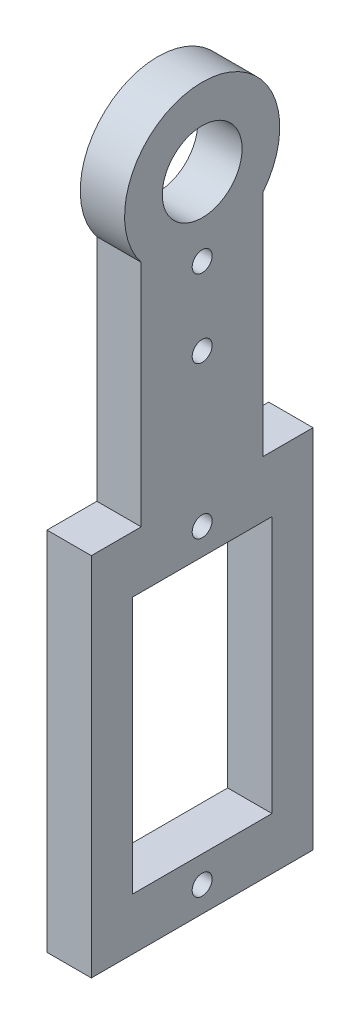
SolidWorks part; units mm, degrees
ref_plane "Front Plane" through (0, 0, 0) normal (0, 0, 1) x (1, 0, 0)
ref_plane "Top Plane" through (0, 0, 0) normal (0, 1, 0) x (1, 0, 0)
ref_plane "Right Plane" through (0, 0, 0) normal (1, 0, 0) x (0, 0, -1)
sketch "Sketch1" plane through (0, 0, 0) normal (1, 0, 0) x (0, 0, -1)
  circle A0 centre (0, 0) radius 7
extrude "Boss-Extrude1" add sketch "Sketch1" along normal blind 4
sketch "Sketch2" plane through (0, 0, 0) normal (0, 0, 1) x (1, 0, 0)
  line L1 (0, -36) -> (4, -36)
  line L2 (0, -36) -> (0, 0)
  line L3 (0, 0) -> (4, 0)
  line L4 (4, -36) -> (4, 0)
extrude "Boss-Extrude2" add sketch "Sketch2" along normal blind 11 from offset 5.5 offset against normal yes
sketch "Sketch3" plane through (0, 0, 0) normal (0, 0, 1) x (1, 0, 0)
  line L1 (0, -58) -> (4, -58)
  line L2 (0, -58) -> (0, -25)
  line L3 (0, -25) -> (4, -25)
  line L4 (4, -58) -> (4, -25)
extrude "Boss-Extrude3" add sketch "Sketch3" along normal blind 20 from offset 10 offset against normal yes
sketch "Sketch4" plane through (0, 0, 0) normal (1, 0, 0) x (0, 0, -1)
  circle A0 centre (0, 0) radius 3.6
extrude "Boss-Extrude4" add sketch "Sketch4" along normal blind 6 from offset 1 separate body offset against normal yes
combine bodies "Combine1" operation type subtract main body 103 bodies to subtract 104
sketch "Sketch5" plane through (0, 0, 0) normal (1, 0, 0) x (0, 0, -1)
  circle A0 centre (0, -7) radius 0.9
extrude "Boss-Extrude5" add sketch "Sketch5" along normal blind 6 from offset 1 separate body offset against normal yes
combine bodies "Combine2" operation type subtract main body 105 bodies to subtract 106
sketch "Sketch6" plane through (0, 0, 0) normal (1, 0, 0) x (0, 0, -1)
  circle A0 centre (0, -14) radius 0.9
extrude "Boss-Extrude6" add sketch "Sketch6" along normal blind 6 from offset 1 separate body offset against normal yes
combine bodies "Combine3" operation type subtract main body 107 bodies to subtract 108
sketch "Sketch7" plane through (0, 0, 0) normal (0, 0, 1) x (1, 0, 0)
  line L1 (-1, -53.3) -> (5, -53.3)
  line L2 (-1, -53.3) -> (-1, -30.1)
  line L3 (-1, -30.1) -> (5, -30.1)
  line L4 (5, -53.3) -> (5, -30.1)
extrude "Boss-Extrude7" add sketch "Sketch7" along normal blind 12.6 from offset 6.3 separate body offset against normal yes
combine bodies "Combine4" operation type subtract main body 109 bodies to subtract 110
sketch "Sketch8" plane through (0, 0, 0) normal (1, 0, 0) x (0, 0, -1)
  circle A0 centre (0, -27.7) radius 0.9
extrude "Boss-Extrude8" add sketch "Sketch8" along normal blind 6 from offset 1 separate body offset against normal yes
combine bodies "Combine5" operation type subtract main body 111 bodies to subtract 112
sketch "Sketch9" plane through (0, 0, 0) normal (1, 0, 0) x (0, 0, -1)
  circle A0 centre (0, -55.7) radius 0.9
extrude "Boss-Extrude9" add sketch "Sketch9" along normal blind 6 from offset 1 separate body offset against normal yes
combine bodies "Combine6" operation type subtract main body 113 bodies to subtract 114
